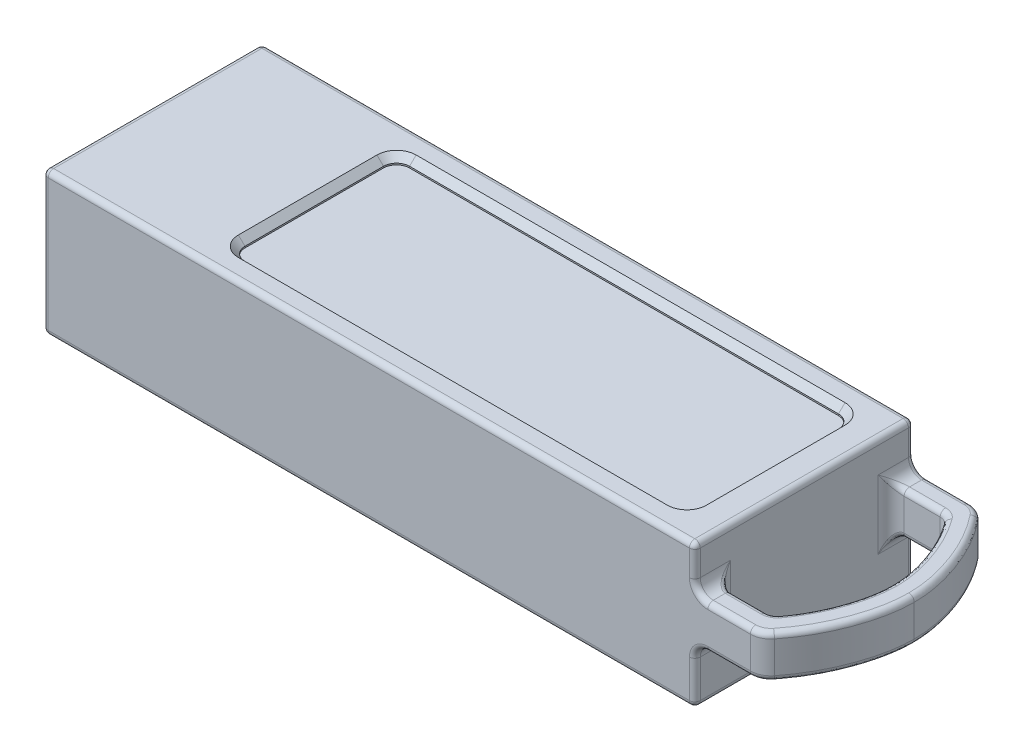
SolidWorks part; units mm, degrees
ref_plane "Front" through (0, 0, 0) normal (0, 0, 1) x (1, 0, 0)
ref_plane "Top" through (0, 0, 0) normal (0, 1, 0) x (1, 0, 0)
ref_plane "Right" through (0, 0, 0) normal (1, 0, 0) x (0, 0, -1)
sketch "Sketch1" plane through (0, 0, 0) normal (0, 1, 0) x (1, 0, 0)
  line L1 (-76.2, -25.6032) -> (76.2, -25.6032)
  line L2 (-76.2, -25.6032) -> (-76.2, 25.6032)
  line L3 (-76.2, 25.6032) -> (76.2, 25.6032)
  line L4 (76.2, -25.6032) -> (76.2, 25.6032)
  line L5 (-76.2, -25.6032) -> (76.2, 25.6032) construction
  line L6 (-76.2, 25.6032) -> (76.2, -25.6032) construction
  point P0 (0, 0)
  dimension "D1" = 51.2064
  dimension "D2" = 152.4
extrude "Boss-Extrude1" add sketch "Sketch1" along normal mid plane 33.401
sketch "Sketch3" plane through (0, 16.7005, 0) normal (0, 1, 0) x (1, 0, 0)
  line L0 (76.2, -25.6032) -> (76.2, 25.6032) construction
  line L1 (67.9831, 19.2405) -> (-38.3667, 19.2405)
  line L2 (67.9831, 19.2405) -> (67.9831, -19.2405)
  line L3 (67.9831, -19.2405) -> (-38.3667, -19.2405)
  line L4 (-38.3667, 19.2405) -> (-38.3667, -19.2405)
  point P6 (67.9831, 0)
  dimension "D1" = 8.2169
  dimension "D2" = 38.481
  dimension "D3" = 106.3498
extrude "Cut-Extrude1" cut sketch "Sketch3" against normal blind 1.8796
fillet "Fillet1" radius 3.048 4 edges at (67.9831, 15.7607, 19.2405) (67.9831, 15.7607, -19.2405) (-38.3667, 15.7607, 19.2405) (-38.3667, 15.7607, -19.2405)
chamfer "Chamfer2" distance 1.524 angle 45 8 edges at (67.9831, 16.7005, 0) (67.0904, 16.7005, -18.3478) (67.0904, 16.7005, 18.3478) (14.8082, 16.7005, -19.2405) (14.8082, 16.7005, 19.2405) (-37.474, 16.7005, -18.3478) (-37.474, 16.7005, 18.3478) (-38.3667, 16.7005, 0)
mirror "Mirror1" about plane through (0, 0, 0) normal (0, 1, 0) of "Cut-Extrude1", "Fillet1"
chamfer "Chamfer3" distance 1.524 angle 45 8 edges at (14.8082, -16.7005, -19.2405) (-37.474, -16.7005, -18.3478) (67.0904, -16.7005, -18.3478) (-38.3667, -16.7005, 0) (67.9831, -16.7005, 0) (-37.474, -16.7005, 18.3478) (67.0904, -16.7005, 18.3478) (14.8082, -16.7005, 19.2405)
sketch "Sketch4" plane through (-76.2, 0, 0) normal (-1, 0, 0) x (0, 0, 1)
  line L0 (-25.6032, -16.7005) -> (25.6032, -16.7005) construction
  line L1 (16.383, 4.1275) -> (-16.383, 4.1275)
  line L2 (19.685, 0.8255) -> (19.685, -8.3185)
  line L3 (16.383, -11.6205) -> (-16.383, -11.6205)
  line L4 (-19.685, 0.8255) -> (-19.685, -8.3185)
  arc A0 (19.685, -8.3185) -> (16.383, -11.6205) centre (16.383, -8.3185) cw
  arc A1 (-16.383, -11.6205) -> (-19.685, -8.3185) centre (-16.383, -8.3185) cw
  arc A2 (16.383, 4.1275) -> (19.685, 0.8255) centre (16.383, 0.8255) cw
  arc A3 (-16.383, 4.1275) -> (-19.685, 0.8255) centre (-16.383, 0.8255) ccw
  point P6 (0, 4.1275)
  point P10 (19.685, -11.6205)
  point P15 (19.685, 4.1275)
  point P18 (-19.685, 4.1275)
  dimension "D4" = 3.302
  dimension "D1" = 15.748
  dimension "D2" = 5.08
  dimension "D3" = 39.37
split line "Split Line1"
sketch "Sketch5" plane through (-76.2, 0, 0) normal (-1, 0, 0) x (0, 0, 1)
  line L1 (-17.653, 1.4732) -> (0.3556, 1.4732)
  line L2 (-17.653, 1.4732) -> (-17.653, -8.9662)
  line L3 (-17.653, -8.9662) -> (0.3556, -8.9662)
  line L4 (0.3556, 1.4732) -> (0.3556, -8.9662)
  line L5 (-19.685, 0.8255) -> (-19.685, -8.3185) construction
  line L6 (19.685, -8.3185) -> (19.685, 0.8255) construction
  line L7 (3.429, 0.0635) -> (17.653, 0.0635)
  line L8 (3.429, 0.0635) -> (3.429, -7.5565)
  line L9 (3.429, -7.5565) -> (17.653, -7.5565)
  line L10 (17.653, 0.0635) -> (17.653, -7.5565)
  point P4 (-17.653, -3.7465)
  point P7 (-19.685, -3.7465)
  point P14 (3.429, -3.7465)
  point P15 (0.3556, -3.7465)
  dimension "D1" = 18.0086
  dimension "D2" = 10.4394
  dimension "D3" = 2.032
  dimension "D4" = 14.224
  dimension "D5" = 7.62
  dimension "D6" = 2.032
extrude "Cut-Extrude2" cut sketch "Sketch5" against normal blind 7.9375
fillet "Fillet3" radius 0.508 8 edges at (-72.2312, -7.5565, 17.653) (-72.2312, -7.5565, 3.429) (-72.2312, 0.0635, 17.653) (-72.2312, 0.0635, 3.429) (-72.2312, -8.9662, 0.3556) (-72.2312, -8.9662, -17.653) (-72.2312, 1.4732, 0.3556) (-72.2312, 1.4732, -17.653)
chamfer "Chamfer4" distance 0.762 angle 45 16 edges at (-76.2, -7.5565, 10.541) (-76.2, -7.4077, 17.5042) (-76.2, -7.4077, 3.5778) (-76.2, -3.7465, 17.653) (-76.2, -3.7465, 3.429) (-76.2, -0.0853, 17.5042) (-76.2, -0.0853, 3.5778) (-76.2, 0.0635, 10.541) (-76.2, -8.9662, -8.6487) (-76.2, -8.8174, 0.2068) (-76.2, -8.8174, -17.5042) (-76.2, -3.7465, 0.3556) (-76.2, -3.7465, -17.653) (-76.2, 1.3244, 0.2068) (-76.2, 1.3244, -17.5042) (-76.2, 1.4732, -8.6487)
sketch "Sketch6" plane through (-68.2625, 0, 0) normal (-1, 0, 0) x (0, 0, 1)
  line L0 (-17.653, 0.9652) -> (-17.653, -8.4582) construction
  line L1 (-16.383, -0.8128) -> (-12.9032, -0.8128)
  line L2 (-16.383, -0.8128) -> (-16.383, -6.6802)
  line L3 (-16.383, -6.6802) -> (-12.9032, -6.6802)
  line L4 (-17.653, 0.9652) -> (-17.653, -8.4582) construction
  arc A0 (-12.9032, -0.8128) -> (-12.9032, -6.6802) centre (-12.9032, -3.7465) cw
  circle A1 centre (-12.9032, -3.7465) radius 2.667
  circle A2 centre (-4.7498, -3.7465) radius 2.9464
  circle A3 centre (-4.7498, -3.7465) radius 2.667
  point P8 (-17.653, -3.7465)
  point P9 (-16.383, -3.7465)
  dimension "D1" = 3.4798
  dimension "D4" = 5.334
  dimension "D5" = 2.2733
  dimension "D6" = 5.8928
  dimension "D7" = 5.334
  dimension "D2" = 5.8674
  dimension "D3" = 1.27
extrude "XT60 Connector Casing" add sketch "Sketch6" along normal offset from surface (7.4295 mm away) 0.508 contours A0 L1 L2 L3 A1 | A2 A3 region at (-68.2625, -0.8997, -14.6431) region at (-68.2625, -3.7465, -7.6129) up to face at (-76.2, 0, 0)
sketch "Sketch7" plane through (-68.2625, 0, 0) normal (-1, 0, 0) x (0, 0, 1)
  circle A24 centre (-12.9032, -3.7465) radius 2.413
  circle A25 centre (-12.9032, -3.7465) radius 2.413
  circle A26 centre (-12.9032, -3.7465) radius 2.159
  circle A27 centre (-4.7498, -3.7465) radius 2.413
  circle A28 centre (-4.7498, -3.7465) radius 2.413
  circle A29 centre (-4.7498, -3.7465) radius 2.159
  dimension "D1" = 0.254
  dimension "D2" = 0.254
  dimension "D3" = 0.254
  dimension "D4" = 0.254
extrude "XT60 Pins" add sketch "Sketch7" along normal offset from surface (6.9215 mm away) 0.508 up to face at (-75.692, -3.7465, -15.5702)
sketch "Sketch9" plane through (-68.2625, 0, 0) normal (-1, 0, 0) x (0, 0, 1)
  line L1 (6.9606, -0.9462) -> (7.547, -0.9462)
  line L2 (6.9606, -0.9462) -> (6.9606, -2.0955)
  line L3 (5.1308, -6.5469) -> (6.123, -6.5469)
  line L4 (7.547, -0.9462) -> (7.547, -2.0955)
  line L5 (13.535, -0.9462) -> (13.535, -2.0955)
  line L6 (8.6788, -2.8124) -> (9.6948, -2.8124)
  line L7 (5.1308, -2.0955) -> (15.9512, -2.0955)
  line L8 (5.1308, -2.0955) -> (5.1308, -5.3975)
  line L9 (5.1308, -5.3975) -> (15.9512, -5.3975)
  line L10 (15.9512, -2.0955) -> (15.9512, -5.3975)
  line L11 (6.123, -2.8124) -> (7.139, -2.8124)
  line L12 (6.123, -2.8124) -> (6.123, -3.8284)
  line L13 (6.123, -3.8284) -> (7.139, -3.8284)
  line L14 (7.139, -2.8124) -> (7.139, -3.8284)
  line L15 (8.6788, -2.8124) -> (8.6788, -3.8284)
  line L16 (8.6788, -3.8284) -> (9.6948, -3.8284)
  line L17 (9.6948, -2.8124) -> (9.6948, -3.8284)
  line L18 (11.2345, -2.8124) -> (12.2505, -2.8124)
  line L19 (11.2345, -2.8124) -> (11.2345, -3.8284)
  line L20 (11.2345, -3.8284) -> (12.2505, -3.8284)
  line L21 (12.2505, -2.8124) -> (12.2505, -3.8284)
  line L22 (13.7902, -2.8124) -> (14.8062, -2.8124)
  line L23 (13.7902, -2.8124) -> (13.7902, -3.8284)
  line L24 (13.7902, -3.8284) -> (14.8062, -3.8284)
  line L25 (14.8062, -2.8124) -> (14.8062, -3.8284)
  line L26 (14.1214, -0.9462) -> (14.1214, -2.0955)
  line L27 (5.1308, -6.5469) -> (5.1308, -5.3975)
  line L28 (6.123, -6.5469) -> (6.123, -5.3975)
  line L29 (7.139, -6.5469) -> (7.139, -5.3975)
  line L30 (8.6788, -6.5469) -> (8.6788, -5.3975)
  line L31 (9.6948, -6.5469) -> (9.6948, -5.3975)
  line L32 (11.2345, -6.5469) -> (11.2345, -5.3975)
  line L33 (12.2505, -6.5469) -> (12.2505, -5.3975)
  line L34 (13.7902, -6.5469) -> (13.7902, -5.3975)
  line L35 (14.8062, -6.5469) -> (14.8062, -5.3975)
  line L36 (10.541, -0.9462) -> (10.541, -6.5469) construction
  line L37 (15.9512, -6.5469) -> (15.9512, -5.3975)
  line L39 (13.535, -0.9462) -> (14.1214, -0.9462)
  line L40 (7.139, -6.5469) -> (8.6788, -6.5469)
  line L41 (9.6948, -6.5469) -> (11.2345, -6.5469)
  line L42 (12.2505, -6.5469) -> (13.7902, -6.5469)
  line L43 (14.8062, -6.5469) -> (15.9512, -6.5469)
  dimension "D3" = 3.302
  dimension "D4" = 1.016
  dimension "D5" = 1.016
  dimension "D6" = 4
extrude "Boss-Extrude4" add sketch "Sketch9" along normal offset from surface (6.4135 mm away) 1.524 contours L3 L28 L9 L27 | L36 L7 L8 L9 L11 L14 L13 L12 L6 L17 L16 L15 | L29 L40 L30 L9 | L9 L36 L41 L32 | L36 L9 L31 L41 | L7 L36 L9 L10 L22 L25 L24 L23 L18 L21 L20 L19 | L33 L42 L34 L9 | L35 L43 L37 L9 region at (-68.2625, -3.8022, 7.8264) region at (-68.2625, -3.8022, 13.2756) region at (-68.2625, -5.9722, 5.6269) region at (-68.2625, -5.9722, 10.1179) region at (-68.2625, -5.9722, 10.8877) region at (-68.2625, -5.9722, 7.9089) region at (-68.2625, -5.9722, 13.0203) region at (-68.2625, -5.9722, 15.3787) up to face at (-76.2, 0, 0)
extrude "Boss-Extrude6" add sketch "Sketch9<5>" along normal offset from surface (5.9055 mm away) 0.508 contours L2 L7 L4 L1 | L39 L5 L7 L26 region at (-68.2625, -1.5208, 7.2538) region at (-68.2625, -1.5208, 13.8282) up to face at (-74.676, -3.3204, 11.7425)
sketch "Sketch9<5>" plane through (-68.2625, 0, 0) normal (-1, 0, 0) x (0, 0, 1) same geometry as "Sketch9"
sketch "Sketch2" plane through (76.2, 0, 0) normal (1, 0, 0) x (0, 0, -1)
  line L0 (25.6032, 16.7005) -> (25.6032, -16.7005) construction
  line L1 (25.6032, 6.4008) -> (-25.6032, 6.4008)
  line L2 (25.6032, 6.4008) -> (25.6032, -3.5687)
  line L3 (25.6032, -3.5687) -> (-25.6032, -3.5687)
  line L4 (-25.6032, 6.4008) -> (-25.6032, -3.5687)
  line L5 (-25.6032, 16.7005) -> (25.6032, 16.7005) construction
  line L6 (-25.6032, 16.7005) -> (-25.6032, -16.7005) construction
  dimension "D1" = 9.9695
  dimension "D3" = 10.2997
extrude "Boss-Extrude7" add sketch "Sketch2" along normal blind 25.6794
sketch "Sketch10" plane through (0, 6.4008, 0) normal (0, 1, 0) x (1, 0, 0)
  line L0 (76.2, 0) -> (101.8794, 0) construction
  line L3 (76.2, 25.6032) -> (76.2, -25.6032) construction
  line L4 (101.8794, 25.6032) -> (101.8794, -25.6032) construction
  line L5 (76.2, 25.6032) -> (89.1783, 25.6032)
  line L7 (76.2, -25.6032) -> (89.1783, -25.6032)
  line L8 (76.2, 20.2692) -> (88.9311, 20.2692)
  line L9 (76.2, -20.2692) -> (88.9311, -20.2692)
  arc A0 (89.1783, 25.6032) -> (92.9662, 23.7676) centre (89.1783, 20.7772) cw
  arc A1 (89.1783, -25.6032) -> (92.9662, -23.7676) centre (89.1783, -20.7772) ccw
  arc A2 (88.9311, 20.2692) -> (88.9311, 20.2692) centre (88.9311, 20.2692) cw
  arc A3 (88.9311, -20.2692) -> (88.9311, -20.2692) centre (88.9311, -20.2692) ccw
  spline S0 degree 3 poles (92.9662, 23.7676) (96.1905, 19.6834) (100.1226, 12.1063) (101.8794, 3.6629) (101.8794, 0) knots 0.081239 0.081239 0.081239 0.081239 0.617185 1 1 1 1
  spline S1 degree 3 poles (92.9662, -23.7676) (96.1905, -19.6834) (100.1226, -12.1063) (101.8794, -3.6629) (101.8794, 0) knots 0.081239 0.081239 0.081239 0.081239 0.617185 1 1 1 1
  spline S2 degree 1 poles (88.9311, 20.2692) (96.5454, 0) knots 0 0 1 1 construction
  spline S3 degree 3 poles (88.9311, 20.2692) (89.5161, 19.5183) (90.6376, 17.9584) (92.57, 14.7795) (94.4989, 10.5947) (96.1315, 5.2293) (96.5454, 1.7631) (96.5454, 0) knots 0.090867 0.090867 0.090867 0.090867 0.204508 0.31815 0.545433 0.772717 1 1 1 1
  spline S4 degree 1 poles (88.9311, -20.2692) (96.5454, 0) knots 0 0 1 1 construction
  spline S5 degree 3 poles (88.9311, -20.2692) (89.5161, -19.5183) (90.6376, -17.9584) (92.57, -14.7795) (94.4989, -10.5947) (96.1315, -5.2293) (96.5454, -1.7631) (96.5454, 0) knots 0.090867 0.090867 0.090867 0.090867 0.204508 0.31815 0.545433 0.772717 1 1 1 1
  line M3 (76.2, 25.6032) -> (76.2, -25.6032)
  line M4 (76.2, -25.6032) -> (101.8794, -25.6032)
  line M5 (101.8794, -25.6032) -> (101.8794, 25.6032)
  line M6 (101.8794, 25.6032) -> (76.2, 25.6032)
  dimension "D1" = 4.826
  dimension "D2" = 5.334
  dimension "D3" = 5.334
extrude "Cut-Extrude3" cut sketch "Sketch10" against normal up to next contours L9 S5 S3 L8 M3 | S1 A1 M4 M5 | A0 S0 M5 M6 region at (98.7331, 6.4008, -19.1693) region at (85.2239, 6.4008, 0) region at (98.7331, 6.4008, 19.1693)
fillet "Fillet4" radius 2.54 2 edges at (88.9311, 1.416, 20.2692) (88.9311, 1.416, -20.2692)
fillet "Fillet5" radius 3.048 6 edges at (76.2, 6.4008, -22.9362) (76.2, -3.5687, -22.9362) (76.2, -3.5687, 22.9362) (76.2, 6.4008, 22.9362) (76.2, 1.416, -20.2692) (76.2, 1.416, 20.2692)
fillet "Fillet6" radius 1.27 36 edges at (77.0927, -4.4614, 19.3765) (83.4553, -3.5687, 20.2692) (88.8177, -3.5687, 19.9914) (77.0927, -4.4614, -19.3765) (83.4553, -3.5687, -20.2692) (88.8177, -3.5687, -19.9914) (77.0927, 7.2935, -19.3765) (83.4553, 6.4008, -20.2692) (88.8177, 6.4008, -19.9914) (77.0927, 7.2935, 19.3765) (83.4553, 6.4008, 20.2692) (88.8177, 6.4008, 19.9914) (76.2, 13.0746, 25.6032) (77.0927, 7.2935, 25.6032) (84.2132, 6.4008, 25.6032) (91.2829, 6.4008, 25.1201) (91.2829, 6.4008, -25.1201) (84.2132, 6.4008, -25.6032) (77.0927, 7.2935, -25.6032) (76.2, -11.6586, 25.6032) (77.0927, -4.4614, 25.6032) (84.2132, -3.5687, 25.6032) (91.2829, -3.5687, 25.1201) (91.2829, -3.5687, -25.1201) (84.2132, -3.5687, -25.6032) (77.0927, -4.4614, -25.6032) (76.2, 13.0747, -25.6032) (76.2, -11.6586, -25.6032)
fillet "Outer Fillet" radius 1.27 14 edges at (-0.635, 16.7005, 25.6032) (-76.2, 16.7005, 0) (-0.635, 16.7005, -25.6032) (76.2, 16.7005, 0) (76.2, -16.7005, 0) (-0.635, -16.7005, 25.6032) (-76.2, -16.7005, 0) (-0.635, -16.7005, -25.6032) (-76.2, 0, -25.6032) (-76.2, 0, 25.6032) (75.828, -16.7005, 25.2312) (75.828, -16.7005, -25.2312) (75.828, 16.7005, -25.2312) (75.828, 16.7005, 25.2312)
